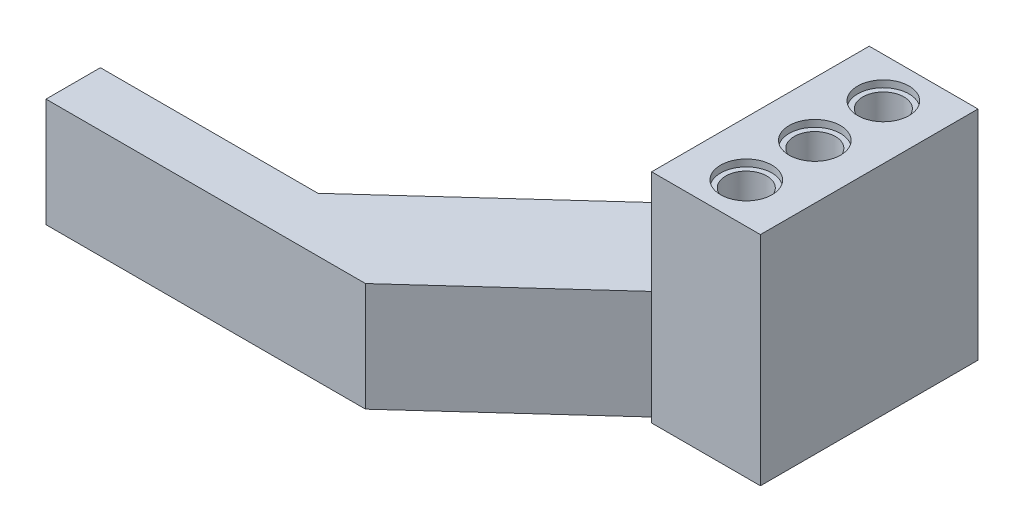
SolidWorks part; units mm, degrees
ref_plane "Front Plane" through (0, 0, 0) normal (0, 0, 1) x (1, 0, 0)
ref_plane "Top Plane" through (0, 0, 0) normal (0, 1, 0) x (1, 0, 0)
ref_plane "Right Plane" through (0, 0, 0) normal (1, 0, 0) x (0, 0, -1)
sketch "Sketch6" plane through (0, 0, 0) normal (0, 1, 0) x (1, 0, 0)
  line L1 (-6.35, 12.7) -> (6.35, 12.7)
  line L2 (-6.35, 12.7) -> (-6.35, -12.7)
  line L3 (-6.35, -12.7) -> (6.35, -12.7)
  line L4 (6.35, 12.7) -> (6.35, -12.7)
  line L5 (-6.35, 12.7) -> (6.35, -12.7) construction
  line L6 (-6.35, -12.7) -> (6.35, 12.7) construction
  point P0 (0, 0)
  dimension "D1" = 12.7
  dimension "D2" = 25.4
extrude "Boss-Extrude1" add sketch "Sketch6" against normal blind 25.4
sketch "Sketch7" plane through (0, 0, 0) normal (0, 1, 0) x (1, 0, 0)
  circle A0 centre (0, 8) radius 2.4
  circle A1 centre (0, 0) radius 2.4
  circle A2 centre (0, -8) radius 2.4
  circle A3 centre (0, 8) radius 3
  circle A4 centre (0, 0) radius 3
  circle A5 centre (0, -8) radius 3
  point P7 (0.6097, 7.9767)
  point P8 (0, 0)
  dimension "D3" = 4.8
  dimension "D1" = 8
  dimension "D2" = 8
  dimension "D4" = 0.6
extrude "Cut-Extrude1" cut sketch "Sketch7" against normal blind 0.8
extrude "Cut-Extrude2" cut sketch "Sketch7<3>" against normal blind 7.2 contours A0 | A1 | A2 region at (0, 0, -8) region at (0, 0, 0) region at (0, 0, 8)
sketch "Sketch7<3>" plane through (0, 0, 0) normal (0, 1, 0) x (1, 0, 0) same geometry as "Sketch7"
sketch "Sketch9" plane through (0, -7.2, -7.2) normal (0, 1, 0) x (1, 0, 0)
  circle A0 centre (0, 0.8) radius 2.4
  circle A1 centre (0, -7.2) radius 2.4
  circle A2 centre (0, -15.2) radius 2.4
  circle A3 centre (0, 0.8) radius 3
  circle A4 centre (0, -7.2) radius 3
  circle A5 centre (0, -15.2) radius 3
  point P7 (0.6097, 7.9767)
  point P8 (0, 0)
  point P15 (0, -7.2)
  dimension "D3" = 4.8
  dimension "D1" = 8
  dimension "D2" = 8
  dimension "D4" = 0.6
extrude "Cut-Extrude4" cut sketch "Sketch9" against normal blind 0.8 contours A3 | A4 | A5
ref_plane "Plane4" through (0, 0, 28) normal (0, 0, 1) x (1, 0, 0)
sketch "Sketch10" plane through (0, -25.4, 0) normal (0, -1, 0) x (-1, 0, 0)
  line L1 (6.35, 5.6187) -> (36.35, -21.65)
  line L3 (36.35, -21.65) -> (61.75, -21.65)
  line L4 (61.75, -21.65) -> (61.75, -28)
  line L5 (-57.9984, -28) -> (57.9984, -28) construction
  line L8 (-6.35, 0) -> (24.4546, -28)
  line L9 (9.0523, -14) -> (17.5945, -4.6021) construction
  line L14 (6.35, 12.7) -> (6.35, -12.7) construction
  line L15 (-6.35, -12.7) -> (-6.35, 12.7) construction
  line L16 (6.35, -12.7) -> (-6.35, -12.7) construction
  line L17 (-6.35, 0) -> (6.35, 5.6187)
  line L18 (24.4546, -28) -> (61.75, -28)
  dimension "D1" = 30
  dimension "D2" = 6.35
  dimension "D3" = 25.4
extrude "Boss-Extrude3" add sketch "Sketch10" against normal blind 12.7
